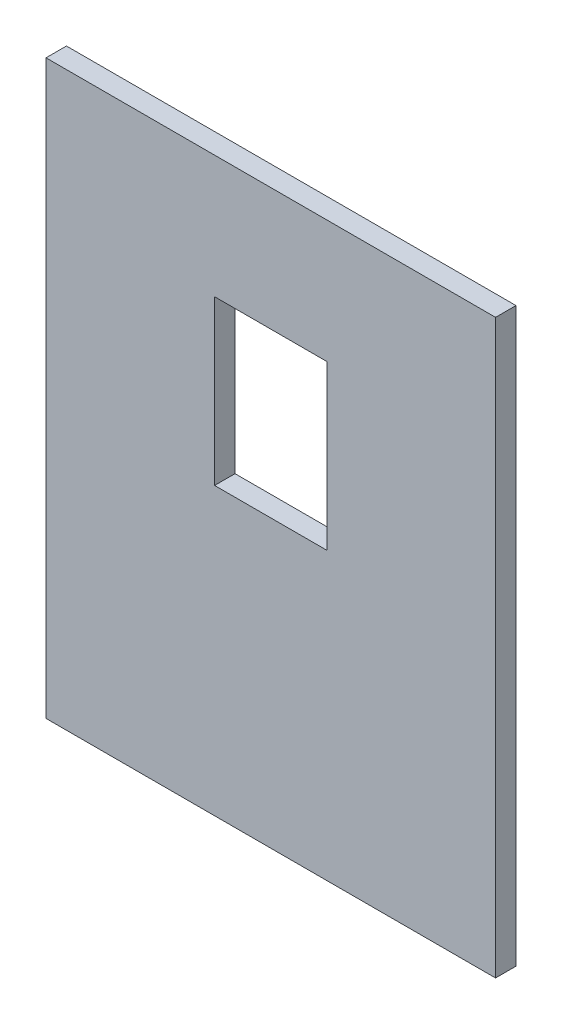
SolidWorks part; units mm, degrees
ref_plane "Front" through (0, 0, 0) normal (0, 0, 1) x (1, 0, 0)
ref_plane "Top" through (0, 0, 0) normal (0, 1, 0) x (1, 0, 0)
ref_plane "Right" through (0, 0, 0) normal (1, 0, 0) x (0, 0, -1)
sketch "Esquisse1" plane through (0, 0, 0) normal (0, 0, 1) x (1, 0, 0)
  line L1 (0, 0) -> (220, 0)
  line L2 (0, 0) -> (0, 280)
  line L3 (0, 280) -> (220, 280)
  line L4 (220, 0) -> (220, 280)
  dimension "D1" = 220
  dimension "D2" = 280
extrude "Boss.-Extru.1" add sketch "Esquisse1" along normal blind 10
sketch "Esquisse2" plane through (0, 0, 0) normal (0, -1, 0) x (1, 0, 0)
  line L0 (0, 5) -> (220, 5) construction
  line L1 (0, 10) -> (0, 0) construction
  line L2 (220, 10) -> (220, 0) construction
  line L3 (110, 5) -> (110, 28.0559) construction
  circle A0 centre (110, 5) radius 2
  circle A1 centre (210, 5) radius 2
  circle A2 centre (10, 5) radius 2
  dimension "D1" = 4
  dimension "D2" = 100
extrude "Enlèv. mat.-Extru.1" cut sketch "Esquisse2" against normal blind 10
sketch "Esquisse3" plane through (0, 0, 10) normal (0, 0, 1) x (1, 0, 0)
  line L0 (110, 0) -> (110, 280) construction
  line L1 (0, 0) -> (220, 0) construction
  line L2 (220, 280) -> (0, 280) construction
  line L3 (82.5, 220) -> (137.5, 220)
  line L4 (137.5, 220) -> (137.5, 140)
  line L5 (137.5, 140) -> (82.5, 140)
  line L6 (82.5, 220) -> (82.5, 140)
  point P11 (110, 140)
  point P12 (110, 220)
  dimension "D1" = 80
  dimension "D2" = 55
  dimension "D3" = 140
extrude "Enlèv. mat.-Extru.2" cut sketch "Esquisse3" against normal through all both and the other way through all
